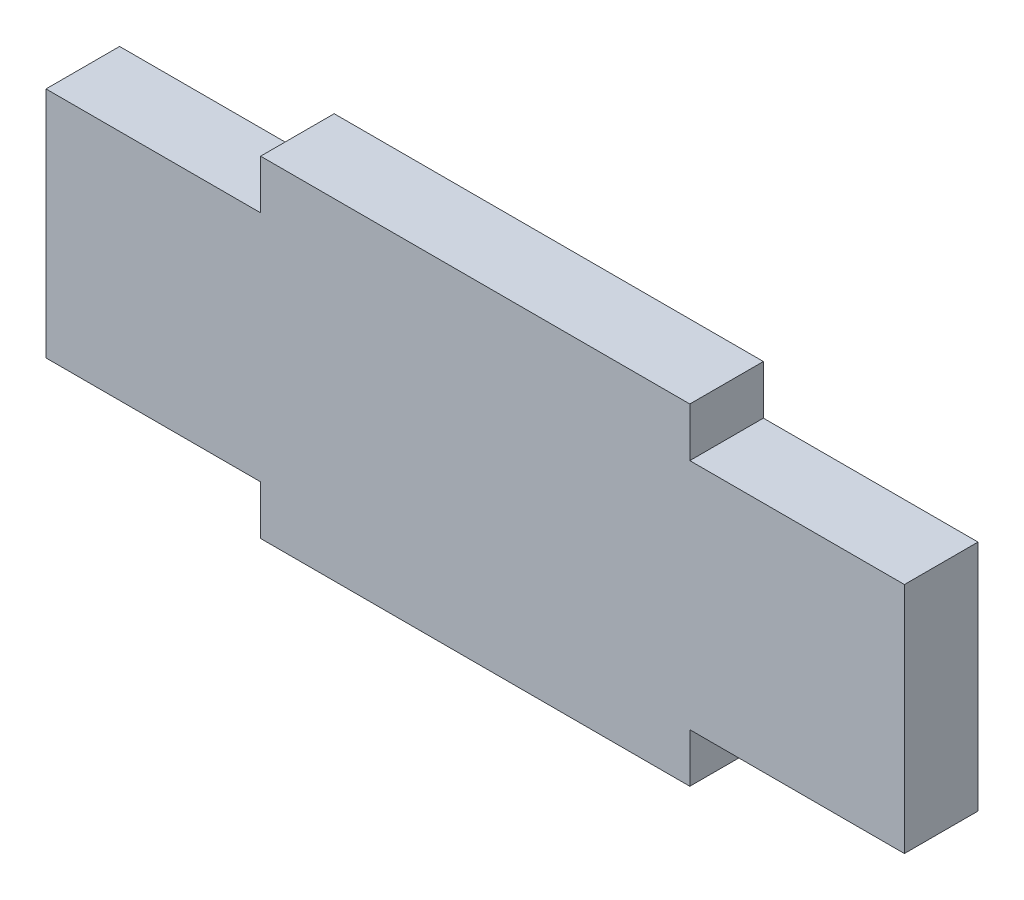
SolidWorks part; units mm, degrees
material "Acrílico (médio-alto impacto)"
ref_plane "Plano frontal" through (0, 0, 0) normal (0, 0, 1) x (1, 0, 0)
ref_plane "Plano superior" through (0, 0, 0) normal (0, 1, 0) x (1, 0, 0)
ref_plane "Plano direito" through (0, 0, 0) normal (1, 0, 0) x (0, 0, -1)
sketch "Esboço1" plane through (0, 0, 0) normal (0, 0, 1) x (1, 0, 0)
  line L0 (0, 0) -> (35, 0) construction
  line L1 (-35, -9.5) -> (35, -9.5)
  line L2 (-35, -9.5) -> (-35, 9.5)
  line L3 (-35, 9.5) -> (35, 9.5)
  line L4 (35, -9.5) -> (35, 9.5)
  line L5 (-35, -9.5) -> (35, 9.5) construction
  line L6 (-35, 9.5) -> (35, -9.5) construction
  line L7 (17.5, 13.5) -> (-17.5, 13.5)
  line L8 (17.5, 13.5) -> (17.5, 9.5)
  line L9 (17.5, 9.5) -> (-17.5, 9.5)
  line L10 (-17.5, 13.5) -> (-17.5, 9.5)
  line L11 (17.5, 13.5) -> (-17.5, 9.5) construction
  line L12 (17.5, 9.5) -> (-17.5, 13.5) construction
  line L13 (17.5, -9.5) -> (-17.5, -9.5)
  line L14 (-17.5, -13.5) -> (-17.5, -9.5)
  line L15 (17.5, -13.5) -> (-17.5, -13.5)
  line L16 (17.5, -13.5) -> (17.5, -9.5)
  point P0 (0, 0)
  point P6 (0, 11.5)
  dimension "D1" = 4
  dimension "D2" = 35
  dimension "D3" = 19
  dimension "D4" = 70
extrude "Ressalto-extrusão1" add sketch "Esboço1" along normal blind 6 contours L1 L4 L3 L2 | L7 L10 L3 L8 | L15 L16 L1 L14 region at (0, 0, 0) region at (0, -11.5, 0) region at (0, 11.5, 0)
